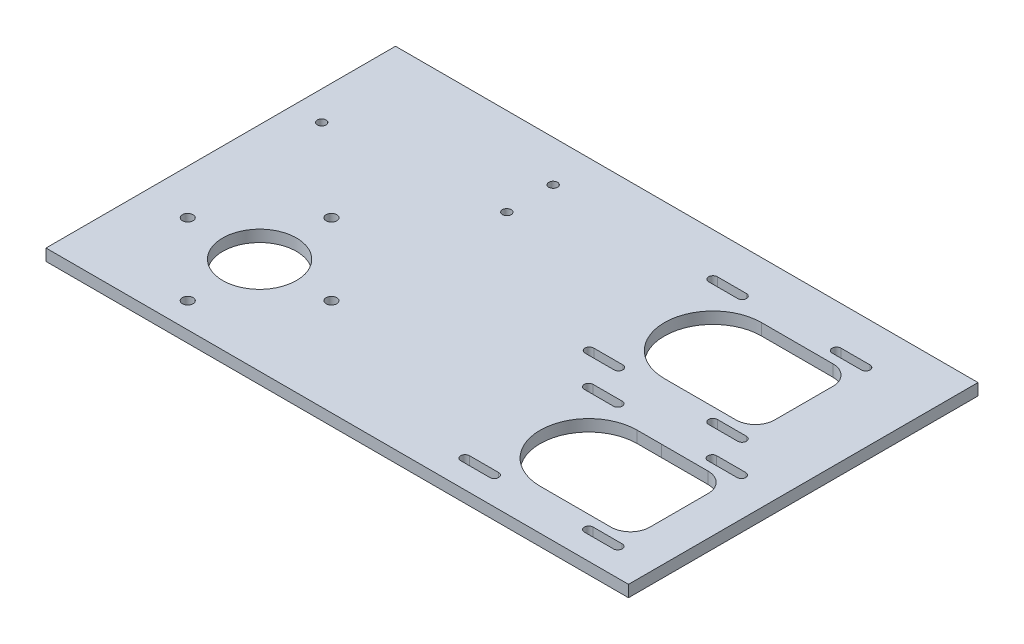
SolidWorks part; units mm, degrees
note: '?' marks a value the reader was unsure of.
ref_plane "Front Plane" through (0, 0, 0) normal (0, 0, 1) x (1, 0, 0)
ref_plane "Top Plane" through (0, 0, 0) normal (0, 1, 0) x (1, 0, 0)
ref_plane "Right Plane" through (0, 0, 0) normal (1, 0, 0) x (0, 0, -1)
ref_axis "X" through (-88.99, 0, 0) along (1, 0, 0)?
ref_axis "Y" through (0, 0, -88.99) along (0, 0, 1)?
ref_axis "Z" through (0, 55, 0) along (0, -1, 0)?
sketch "Sketch1" plane through (0, 0, 0) normal (0, 1, 0) x (1, 0, 0)
  line L1 (-100, -50) -> (190, -50)
  line L2 (-100, -50) -> (-100, 130)
  line L3 (-100, 130) -> (190, 130)
  line L4 (190, -50) -> (190, 130)
  point P0 (0, 0)
  dimension "D1" = 130
  dimension "D2" = 100
  dimension "D3" = 50
  dimension "D4" = 190
extrude "Boss-Extrude1" add sketch "Sketch1" along normal blind 6
sketch "Sketch2" plane through (0, 6, 0) normal (0, 1, 0) x (1, 0, 0)
  line L0 (-50, 0) -> (0, 0) construction
  line L1 (0, 0) -> (54.6998, -24.6563) construction
  circle A0 centre (-50, 0) radius 19
  circle A1 centre (54.6998, -24.6563) radius 18.1 construction
  dimension "D1" = 38
  dimension "D4" = 36.2
  dimension "D2" = 50
extrude "Cut-Extrude1" cut sketch "Sketch2" against normal through all
hole_wizard "M4 Clearance Hole1" positions "Sketch3" profile "Sketch4" hole size "M4" standard "DIN" end condition through all
sketch "Sketch3" plane through (0, 6, 0) normal (0, 1, 0) x (1, 0, 0)
  line L0 (-100, 130) -> (-100, -50) construction
  line L1 (190, 130) -> (-100, 130) construction
  line L7 (-95, 77) -> (-7.3349, 84.6697) construction
  line L10 (-95, 77) -> (-7.6086, 108.8079) construction
  line L12 (-95, 77) -> (-95, 105.8153) construction
  point P0 (-95, 77)
  point P7 (-7.6086, 108.8079)
  point P9 (-7.3349, 84.6697)
  dimension "D1" = 5
  dimension "D2" = 53
  dimension "D3" = 70
  dimension "D4" = 85
  dimension "D5" = 88
  dimension "D6" = 93
sketch "Sketch4" plane through (-95, 6, -77) normal (1, 0, 0) x (0, 0, 1)
  line L0 (0, 0) -> (0, 6)
  line L1 (0, 6) -> (2.25, 6)
  line L2 (2.25, 6) -> (2.25, 0)
  line L5 (2.25, 0) -> (0, 0)
  line L11 (0, -6.35) -> (0, 107.95) construction
  dimension "Thru Hole Dia." = 4.5
  dimension "Thru Hole Depth" = 6
sketch "Sketch5" plane through (0, 6, 0) normal (0, 1, 0) x (1, 0, 0)
  line L0 (90, -20) -> (90, 65) construction
  circle A0 centre (90, 65) radius 8
  circle A1 centre (90, -20) radius 8
  circle A2 centre (-50, 0) radius 19 construction
  dimension "D1" = 16
  dimension "D2" = 16
  dimension "D3" = 140
  dimension "D5" = 85
  dimension "D4" = 20
extrude "Cut-Extrude2" [suppressed] cut sketch "Sketch5" against normal through all
hole_wizard "M5 Clearance Hole1" [suppressed] positions "Sketch6" profile "Sketch7" hole size "M5" standard "DIN"
sketch "Sketch6" plane through (0, 6, 0) normal (0, 1, 0) x (1, 0, 0)
  circle A0 centre (-50, 0) radius 17.5 construction
  point P0 (110, -80)
  point P6 (140, 105)
  dimension "D1" = 80
  dimension "D2" = 160
  dimension "D3" = 105
  dimension "D4" = 190
sketch "Sketch7" plane through (110, 6, 80) normal (1, 0, 0) x (0, 0, 1)
  line L0 (0, 0) -> (0, 6)
  line L1 (0, 6) -> (2.75, 6)
  line L2 (2.75, 6) -> (2.75, 0)
  line L5 (2.75, 0) -> (0, 0)
  line L11 (0, -6.35) -> (0, 107.95) construction
  dimension "Thru Hole Dia." = 5.5
  dimension "Thru Hole Depth" = 6
sketch "Sketch8" plane through (0, 6, 0) normal (0, 1, 0) x (1, 0, 0)
  line L0 (75.6802, 107.8198) -> (90.6802, 107.8198) construction
  line L1 (75.6802, 110.0698) -> (90.6802, 110.0698)
  line L2 (75.6802, 105.5698) -> (90.6802, 105.5698)
  line L3 (139.3198, 107.8198) -> (154.3198, 107.8198) construction
  line L4 (139.3198, 110.0698) -> (154.3198, 110.0698)
  line L5 (139.3198, 105.5698) -> (154.3198, 105.5698)
  line L6 (83.1802, 107.8198) -> (83.1802, 44.1802) construction
  line L7 (75.6802, 44.1802) -> (90.6802, 44.1802) construction
  line L8 (75.6802, 46.4302) -> (90.6802, 46.4302)
  line L9 (75.6802, 41.9302) -> (90.6802, 41.9302)
  line L10 (139.3198, 44.1802) -> (154.3198, 44.1802) construction
  line L11 (139.3198, 46.4302) -> (154.3198, 46.4302)
  line L12 (139.3198, 41.9302) -> (154.3198, 41.9302)
  line L13 (83.1802, 107.8198) -> (146.8198, 107.8198) construction
  line L14 (83.1802, 107.8198) -> (146.8198, 44.1802) construction
  line L15 (107.5, 76) -> (122.5, 76) construction
  line L16 (107.5, 101) -> (122.5, 101)
  line L17 (107.5, 51) -> (122.5, 51)
  line L19 (-100, -50) -> (190, -50) construction
  arc A0 (75.6802, 110.0698) -> (75.6802, 105.5698) centre (75.6802, 107.8198) ccw
  arc A1 (90.6802, 105.5698) -> (90.6802, 110.0698) centre (90.6802, 107.8198) ccw
  arc A2 (139.3198, 110.0698) -> (139.3198, 105.5698) centre (139.3198, 107.8198) ccw
  arc A3 (154.3198, 105.5698) -> (154.3198, 110.0698) centre (154.3198, 107.8198) ccw
  arc A4 (75.6802, 46.4302) -> (75.6802, 41.9302) centre (75.6802, 44.1802) ccw
  arc A5 (90.6802, 41.9302) -> (90.6802, 46.4302) centre (90.6802, 44.1802) ccw
  arc A6 (139.3198, 46.4302) -> (139.3198, 41.9302) centre (139.3198, 44.1802) ccw
  arc A7 (154.3198, 41.9302) -> (154.3198, 46.4302) centre (154.3198, 44.1802) ccw
  arc A8 (107.5, 101) -> (107.5, 51) centre (107.5, 76) ccw
  arc A9 (122.5, 51) -> (122.5, 101) centre (122.5, 76) ccw
  circle A10 centre (-50, 0) radius 19 construction
  point P2 (83.1802, 107.8198)
  point P8 (146.8198, 107.8198)
  point P18 (83.1802, 44.1802)
  point P24 (146.8198, 44.1802)
  point P34 (115, 76)
  dimension "D1" = 4.5
  dimension "D2" = 15
  dimension "D3" = 90
  dimension "D4" = 50
  dimension "D5" = 165
  dimension "D6" = 126
extrude "Cut-Extrude3" cut sketch "Sketch8" against normal blind 10
sketch "Sketch9" plane through (0, 6, 0) normal (0, 1, 0) x (1, 0, 0)
  line L0 (91.6802, 27.8198) -> (106.6802, 27.8198) construction
  line L1 (91.6802, 30.0698) -> (106.6802, 30.0698)
  line L2 (91.6802, 25.5698) -> (106.6802, 25.5698)
  line L3 (155.3198, 27.8198) -> (170.3198, 27.8198) construction
  line L4 (155.3198, 30.0698) -> (170.3198, 30.0698)
  line L5 (155.3198, 25.5698) -> (170.3198, 25.5698)
  line L6 (99.1802, 27.8198) -> (99.1802, -35.8198) construction
  line L7 (91.6802, -35.8198) -> (106.6802, -35.8198) construction
  line L8 (91.6802, -33.5698) -> (106.6802, -33.5698)
  line L9 (91.6802, -38.0698) -> (106.6802, -38.0698)
  line L10 (155.3198, -35.8198) -> (170.3198, -35.8198) construction
  line L11 (155.3198, -33.5698) -> (170.3198, -33.5698)
  line L12 (155.3198, -38.0698) -> (170.3198, -38.0698)
  line L13 (99.1802, 27.8198) -> (162.8198, 27.8198) construction
  line L14 (99.1802, 27.8198) -> (162.8198, -35.8198) construction
  line L15 (123.5, -4) -> (138.5, -4) construction
  line L16 (123.5, 21) -> (138.5, 21)
  line L17 (123.5, -29) -> (138.5, -29)
  line L19 (-100, -50) -> (190, -50) construction
  arc A0 (91.6802, 30.0698) -> (91.6802, 25.5698) centre (91.6802, 27.8198) ccw
  arc A1 (106.6802, 25.5698) -> (106.6802, 30.0698) centre (106.6802, 27.8198) ccw
  arc A2 (155.3198, 30.0698) -> (155.3198, 25.5698) centre (155.3198, 27.8198) ccw
  arc A3 (170.3198, 25.5698) -> (170.3198, 30.0698) centre (170.3198, 27.8198) ccw
  arc A4 (91.6802, -33.5698) -> (91.6802, -38.0698) centre (91.6802, -35.8198) ccw
  arc A5 (106.6802, -38.0698) -> (106.6802, -33.5698) centre (106.6802, -35.8198) ccw
  arc A6 (155.3198, -33.5698) -> (155.3198, -38.0698) centre (155.3198, -35.8198) ccw
  arc A7 (170.3198, -38.0698) -> (170.3198, -33.5698) centre (170.3198, -35.8198) ccw
  arc A8 (123.5, 21) -> (123.5, -29) centre (123.5, -4) ccw
  arc A9 (138.5, -29) -> (138.5, 21) centre (138.5, -4) ccw
  circle A10 centre (-50, 0) radius 19 construction
  point P2 (99.1802, 27.8198)
  point P8 (162.8198, 27.8198)
  point P18 (99.1802, -35.8198)
  point P24 (162.8198, -35.8198)
  point P34 (131, -4)
  dimension "D1" = 4.5
  dimension "D2" = 15
  dimension "D3" = 90
  dimension "D4" = 50
  dimension "D5" = 46
  dimension "D6" = 15
  dimension "D7" = 181
extrude "Cut-Extrude4" cut sketch "Sketch9" against normal blind 10
sketch "Sketch10" plane through (0, 6, 0) normal (0, 1, 0) x (1, 0, 0)
  line L7 (123.5, 21) -> (123.5, -4) construction
  point P0 (123.5, -4)
  line B0 (123.5, -4) -> (148.5, -4) construction
  line B1 (123.5, 21) -> (136, 21.0049)
  line B2 (123.5, -29) -> (136, -29)
  line B3 (136, -29) -> (136, 21.0049) construction
  line B4 (136, 21.0049) -> (170, 21.0049)
  line B5 (170, 21.0049) -> (170, -29)
  line B6 (170, -29) -> (136, -29)
  arc B7 (123.5, 21) -> (123.5, -29) centre (123.5, -4) ccw
sketch_block_instance "Block1-1"
sketch_block "Block1" parameters "D1"=25, "D2"=34
extrude "Cut-Extrude5" cut sketch "Sketch10" against normal through all
fillet "Fillet1" radius 10 2 edges at (170, 3, 29) (170, 3, -21.0049)
sketch "Sketch12" plane through (0, 6, 0) normal (0, 1, 0) x (1, 0, 0)
  line L0 (107.5, 51) -> (122.5, 51) construction
  line L1 (115, 51) -> (154.3198, 51)
  line L2 (115, 51) -> (115, 101)
  line L3 (115, 101) -> (154.3198, 101)
  line L4 (154.3198, 51) -> (154.3198, 101)
  line L5 (122.5, 101) -> (107.5, 101) construction
extrude "Cut-Extrude6" cut sketch "Sketch12" against normal blind 10
fillet "Fillet2" radius 10 2 edges at (154.3198, 3, -101) (154.3198, 3, -51)
ref_axis "Axis1" through (-50, 0, 0) along (0, 1, 0)?
sketch "Sketch13" plane through (0, 6, 0) normal (0, 1, 0) x (1, 0, 0)
  point P0 (-13, 0)
  dimension "D1" = 37
hole_wizard "M5 Clearance Hole2" positions "3DSketch1" profile "Sketch14" hole size "M5" standard "ANSI Metric"
sketch3d "3DSketch1"
  point P0 (-13, 6, 0)
sketch "Sketch14" plane through (-13, 6, 0) normal (1, 0, 0) x (0, 0, 1)
  line L0 (0, 0) -> (0, 21.6524)
  line L1 (0, 21.6524) -> (2.75, 20)
  line L2 (2.75, 20) -> (2.75, 0)
  line L5 (2.75, 0) -> (0, 0)
  line L10 (0, 21.6524) -> (-2.75, 20) construction
  line L11 (0, -6.35) -> (0, 107.95) construction
  dimension "Hole Dia." = 5.5
  dimension "Hole Depth" = 20
  dimension "Drill Angle" = 118
pattern_circular "CirPattern1" count 4 over 360 about axis through (-50, 0, 0) along (0, 1, 0) of "M5 Clearance Hole2"
sketch "Sketch15" plane through (-100, 0, 0) normal (-1, 0, 0) x (0, 0, 1)
  line L4 (-130, 0) -> (50, 0)
  line L5 (50, 0) -> (50, 6)
  line L6 (50, 6) -> (-130, 6)
  line L7 (-130, 6) -> (-130, 0)
  line L8 (-130, 0) -> (50, 0)
  line L9 (50, 0) -> (50, 6)
  line L10 (50, 6) -> (-130, 6)
  line L11 (-130, 6) -> (-130, 0)
  dimension "D1" = 0
extrude "Boss-Extrude2" add sketch "Sketch15" along normal blind 10
